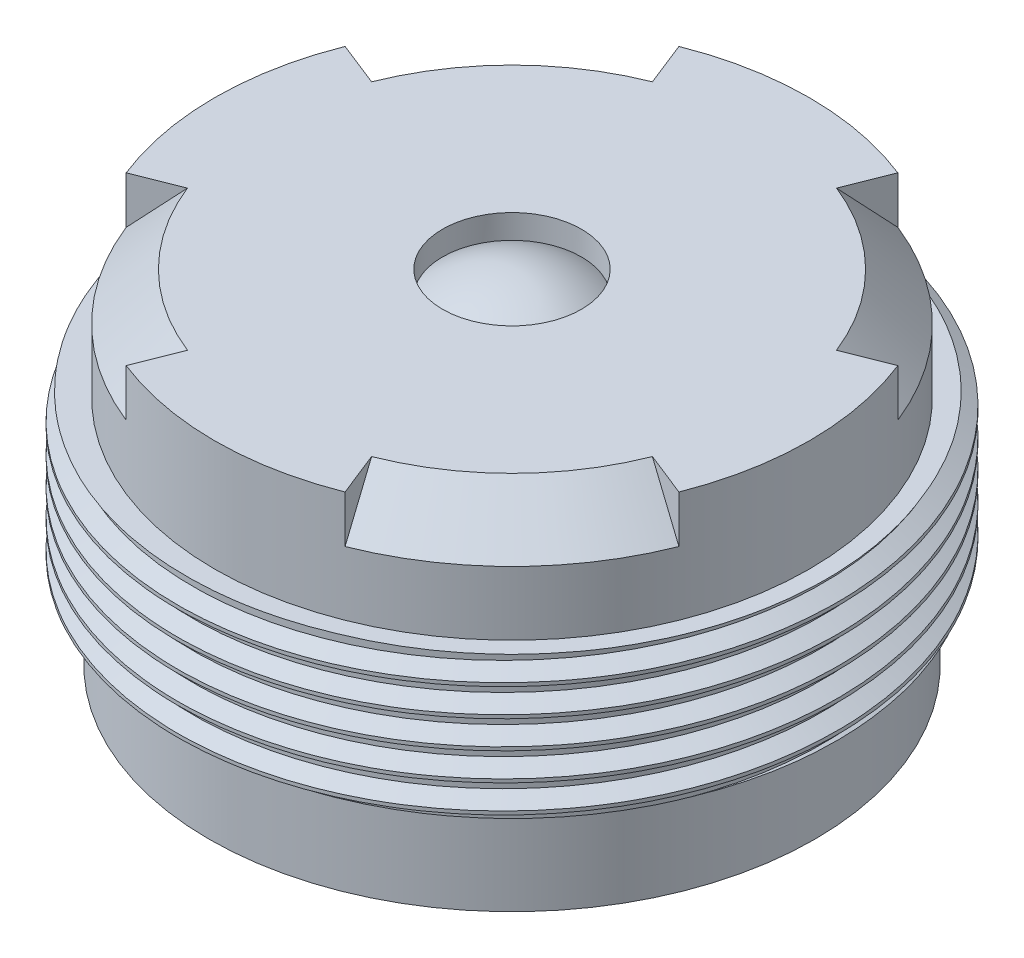
SolidWorks part; units mm, degrees
ref_plane "Front Plane" through (0, 0, 0) normal (0, 0, 1) x (1, 0, 0)
ref_plane "Top Plane" through (0, 0, 0) normal (0, 1, 0) x (1, 0, 0)
ref_plane "Right Plane" through (0, 0, 0) normal (1, 0, 0) x (0, 0, -1)
sketch "Sketch1" plane through (0, 0, 0) normal (0, 1, 0) x (1, 0, 0)
  circle A0 centre (0, 0) radius 2.725
  dimension "D1" = 5.45
extrude "Boss-Extrude1" add sketch "Sketch1" along normal blind 3.08
sketch "Sketch2" plane through (0, 0, 0) normal (0, -1, 0) x (1, 0, 0)
  circle A0 centre (0, 0) radius 2.11
  dimension "D1" = 4.22
extrude "Cut-Extrude1" cut sketch "Sketch2" against normal blind 2.08
sketch "Sketch3" plane through (0, 3.08, 0) normal (0, 1, 0) x (1, 0, 0)
  circle A0 centre (0, 0) radius 0.625
  dimension "D1" = 1.25
extrude "Cut-Extrude2" cut sketch "Sketch3" against normal up to next
sketch "Sketch4" plane through (0, 3.08, 0) normal (0, 1, 0) x (1, 0, 0)
  circle A0 centre (0, 0) radius 2.675
  circle A1 centre (0, 0) radius 2.725
  dimension "D1" = 5.35
extrude "Cut-Extrude3" cut sketch "Sketch4" against normal blind 1
sketch "Sketch5" plane through (0, 3.08, 0) normal (0, 1, 0) x (1, 0, 0)
  line L0 (0, 0) -> (0, 2.675) construction
  line L1 (0, 0) -> (0.985, 2.487)
  line L2 (0, 0) -> (-0.985, 2.487)
  line L3 (-0.985, 2.487) -> (0.985, 2.487) construction
  line L4 (0, 0) -> (2.487, -0.985)
  line L5 (0, 0) -> (2.487, 0.985)
  line L6 (0, 0) -> (-0.985, -2.487)
  line L7 (0, 0) -> (0.985, -2.487)
  line L8 (0, 0) -> (-2.487, 0.985)
  line L9 (0, 0) -> (-2.487, -0.985)
  circle A0 centre (0, 0) radius 2.675
  circle A1 centre (0, 0) radius 2.25
  circle A2 centre (0, 0) radius 2.675 construction
  point P3 (0, 2.487)
  point P19 (0, 0)
  dimension "D2" = 4.5
  dimension "D1" = 1.97
  dimension "D3" = 4
sketch "Sketch6" plane through (0, 3.08, 0) normal (0, 1, 0) x (1, 0, 0)
  line L0 (0, 0) -> (2.487, 0.985) construction
  line L1 (0, 0) -> (2.487, -0.985) construction
  line L2 (0, 0) -> (0.985, -2.487) construction
  line L3 (0, 0) -> (-0.985, -2.487) construction
  line L4 (0, 0) -> (-2.487, -0.985) construction
  line L5 (0, 0) -> (-2.487, 0.985) construction
  line L6 (0, 0) -> (-0.985, 2.487) construction
  line L7 (0, 0) -> (0.985, 2.487) construction
  line L8 (2.0919, 0.8285) -> (2.487, 0.985)
  line L9 (2.0919, -0.8285) -> (2.487, -0.985)
  line L10 (0.8285, -2.0919) -> (0.985, -2.487)
  line L11 (-0.8285, -2.0919) -> (-0.985, -2.487)
  line L12 (-2.0919, -0.8285) -> (-2.487, -0.985)
  line L13 (-2.0919, 0.8285) -> (-2.487, 0.985)
  line L14 (-0.8285, 2.0919) -> (-0.985, 2.487)
  line L15 (0.8285, 2.0919) -> (0.985, 2.487)
  circle A0 centre (0, 0) radius 2.675 construction
  circle A1 centre (0, 0) radius 2.25 construction
  arc A2 (-0.985, 2.487) -> (-2.487, 0.985) centre (0, 0) ccw
  arc A3 (-0.8285, 2.0919) -> (-2.0919, 0.8285) centre (0, 0) ccw
  arc A4 (2.0919, 0.8285) -> (0.8285, 2.0919) centre (0, 0) ccw
  arc A5 (2.487, 0.985) -> (0.985, 2.487) centre (0, 0) ccw
  arc A6 (-2.0919, -0.8285) -> (-0.8285, -2.0919) centre (0, 0) ccw
  arc A7 (-2.487, -0.985) -> (-0.985, -2.487) centre (0, 0) ccw
  arc A8 (0.8285, -2.0919) -> (2.0919, -0.8285) centre (0, 0) ccw
  arc A9 (0.985, -2.487) -> (2.487, -0.985) centre (0, 0) ccw
extrude "Cut-Extrude4" cut sketch "Sketch6" against normal blind 1
sketch "Sketch7" plane through (0, 2.08, 0) normal (0, 1, 0) x (1, 0, 0)
  line L0 (2.487, -0.985) -> (2.0919, -0.8285) construction
  line L1 (0.8285, -2.0919) -> (0.985, -2.487) construction
  line L2 (2.487, -0.985) -> (2.0919, -0.8285)
  line L3 (0.8285, -2.0919) -> (0.985, -2.487)
  line L4 (2.0919, 0.8285) -> (2.487, 0.985) construction
  line L5 (0.985, 2.487) -> (0.8285, 2.0919) construction
  line L6 (2.0919, 0.8285) -> (2.487, 0.985)
  line L7 (0.985, 2.487) -> (0.8285, 2.0919)
  line L8 (-0.8285, 2.0919) -> (-0.985, 2.487) construction
  line L9 (-2.487, 0.985) -> (-2.0919, 0.8285) construction
  line L10 (-0.8285, 2.0919) -> (-0.985, 2.487)
  line L11 (-2.487, 0.985) -> (-2.0919, 0.8285)
  line L12 (-2.0919, -0.8285) -> (-2.487, -0.985) construction
  line L13 (-0.985, -2.487) -> (-0.8285, -2.0919) construction
  line L14 (-2.0919, -0.8285) -> (-2.487, -0.985)
  line L15 (-0.985, -2.487) -> (-0.8285, -2.0919)
  circle A0 centre (0, 0) radius 2.25 construction
  circle A1 centre (0, 0) radius 2.675 construction
  arc A2 (0.8285, -2.0919) -> (2.0919, -0.8285) centre (0, 0) ccw
  arc A3 (0.985, -2.487) -> (2.487, -0.985) centre (0, 0) ccw
  arc A4 (-0.8285, 2.0919) -> (-2.0919, 0.8285) centre (0, 0) ccw
  arc A5 (-0.985, 2.487) -> (-2.487, 0.985) centre (0, 0) ccw
  arc A6 (-2.487, -0.985) -> (-0.985, -2.487) centre (0, 0) ccw
  arc A7 (-2.0919, -0.8285) -> (-0.8285, -2.0919) centre (0, 0) ccw
  arc A8 (2.0919, 0.8285) -> (0.8285, 2.0919) centre (0, 0) ccw
  arc A9 (2.487, 0.985) -> (0.985, 2.487) centre (0, 0) ccw
extrude "Boss-Extrude2" add sketch "Sketch7" along normal blind 0.5
chamfer "Chamfer1" distance 0.5 4 edges at (-1.591, 2.58, 1.591) (-1.591, 2.58, -1.591) (1.591, 2.58, -1.591) (1.591, 2.58, 1.591)
ref_plane "Plane1" through (0, 0.8, 0) normal (0, 1, 0) x (1, 0, 0)
sketch "Sketch8" plane through (0, 0.8, 0) normal (0, 1, 0) x (1, 0, 0)
  circle A0 centre (0, 0) radius 2.965
  circle A1 centre (0, 0) radius 2.11 construction
  circle A2 centre (0, 0) radius 2.11
  dimension "D1" = 5.93
extrude "Boss-Extrude3" add sketch "Sketch8" along normal up to surface (1.28 mm away) up to face at (0, 2.08, 2.725)
thread "Thread1" pitch 0.25 method cut profile "Thread Profile1" start angle 0, offset 0.5, length 2, pitch 0.25, diameter 5.93
ref_plane "Plane2" through (-2.965, 2.58, 0) normal (0, 0, 1) x (-1, 0, 0)
sketch "Thread Profile1" plane through (-2.965, 2.58, 0) normal (0, 0, 1) x (-1, 0, 0)
  line L0 (0, 0) -> (0, 0.25) construction
  line L11 (0, 0) -> (0, 0.2187)
  line L12 (0, 0.2187) -> (-0.1353, 0.1406)
  line L13 (-0.1353, 0.1406) -> (-0.1353, 0.0781)
  line L15 (-0.1353, 0.0781) -> (0, 0)
  line L17 (-0.1353, 0.1094) -> (0, 0.1094) construction
  point P2 (0, 0)
  dimension "Pitch" = 0.25
  dimension "Profile_Angle" = 60
  dimension "Profile_Land" = 0.0625
  dimension "Profile_Height" = 0.1353
sketch "Sketch11" plane through (0, 0, 0) normal (0, 0, 1) x (1, 0, 0)
  line L0 (0, 0) -> (0, 3.08) construction
  line L1 (-0.8285, 3.08) -> (-0.985, 3.08) construction
sketch "Sketch12" plane through (0, 0, 0) normal (1, 0, 0) x (0, 0, -1)
  line L0 (0.625, 3.08) -> (-0.625, 3.08) construction
  line L1 (0.625, 3.08) -> (-0.625, 3.08) construction
  line L2 (-0.625, 2.8635) -> (0.625, 2.8635) construction
  line L3 (0, 0) -> (0, 3.08) construction
  line L4 (-0.625, 2.651) -> (0.625, 2.651) construction
  line L5 (-0.625, 2.8635) -> (-0.625, 2.651) construction
  line L6 (0.625, 2.8635) -> (0.625, 2.651)
  line L7 (-0.625, 2.7572) -> (0.625, 2.7572) construction
  line L8 (0, 3.08) -> (0, 2.8635) construction
  line L9 (0, 2.651) -> (0, 2.4344) construction
  line L10 (0, 3.08) -> (0, 2.4344)
  spline S0 degree 2 poles (0.625, 2.8635) (0.3125, 3.08) (0, 3.08) knots 0 0 0 0.5 0.5 0.5
  spline S1 degree 2 poles (0, 2.4344) (0.3125, 2.4344) (0.625, 2.651) knots 0.5 0.5 0.5 1 1 1
  point P4 (0, 2.8635)
revolve "Revolve4" add sketch "Sketch12" angle 360 about L0
